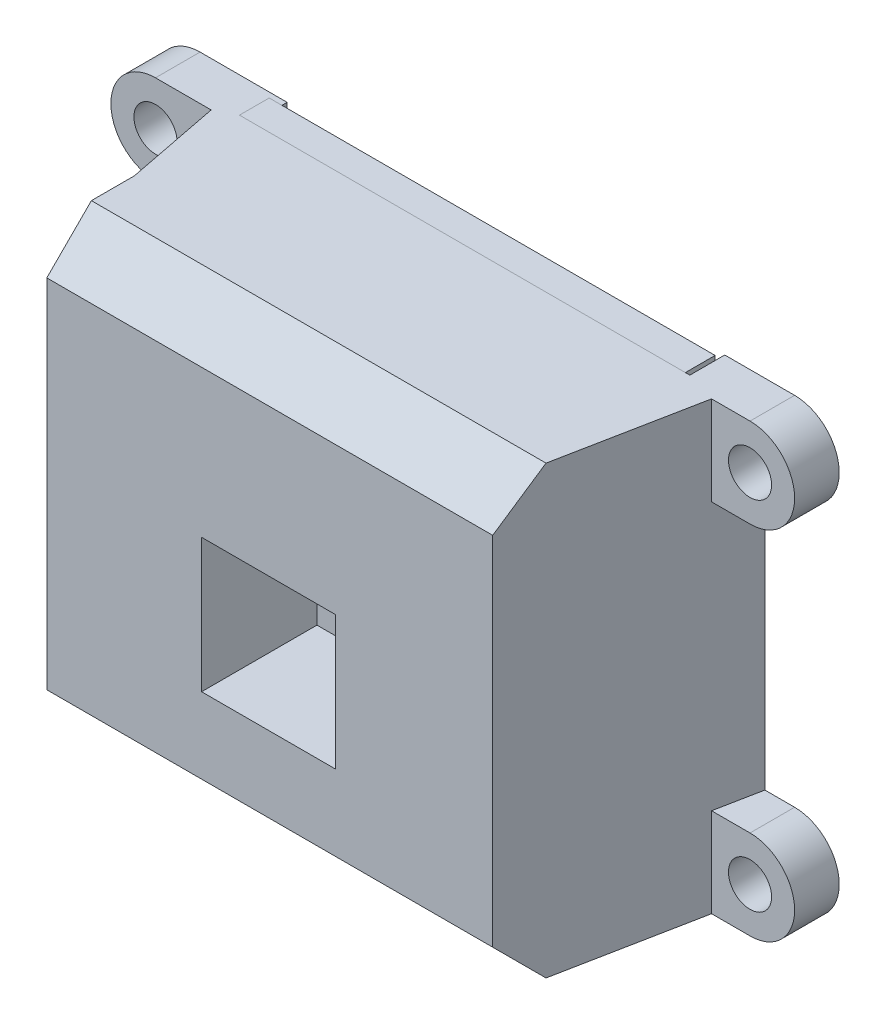
SolidWorks part; units mm, degrees
ref_plane "Front Plane" through (0, 0, 0) normal (0, 0, 1) x (1, 0, 0)
ref_plane "Top Plane" through (0, 0, 0) normal (0, 1, 0) x (1, 0, 0)
ref_plane "Right Plane" through (0, 0, 0) normal (1, 0, 0) x (0, 0, -1)
sketch "Sketch1" plane through (0, 0, 6.763) normal (0, 0, 1) x (1, 0, 0)
  line L1 (-15, -15) -> (15, -15)
  line L2 (-15, -15) -> (-15, 15)
  line L3 (-15, 15) -> (15, 15)
  line L4 (15, -15) -> (15, 15)
  line L5 (-15, -15) -> (15, 15) construction
  line L6 (-15, 15) -> (15, -15) construction
  point P0 (0, 0)
  dimension "D1" = 30
extrude "Boss-Extrude1" add sketch "Sketch1" along normal blind 2
sketch "Sketch2" plane through (0, 0, 6.763) normal (0, 0, -1) x (-1, 0, 0)
  line L0 (13, -15) -> (13, 13)
  line L1 (13, 13) -> (-13, 13)
  line L2 (-13, 13) -> (-13, -15)
  line L3 (-15, -15) -> (-13, -15)
  line L4 (-15, 15) -> (-15, -15)
  line L5 (-15, -15) -> (15, -15)
  line L6 (15, -15) -> (15, 15)
  line L7 (15, 15) -> (-15, 15)
  line L8 (-15, 15) -> (-15, -15)
  line L10 (15, -15) -> (15, 15)
  line L11 (15, 15) -> (-15, 15)
  line L12 (13, -15) -> (15, -15)
  dimension "D1" = 0
  dimension "D2" = 2
extrude "Boss-Extrude2" add sketch "Sketch2" along normal offset from surface (10.963 mm away) 1 offset beyond the face yes
sketch "Sketch3" plane through (0, 0, 6.763) normal (0, 0, -1) x (-1, 0, 0)
  line L0 (-10.4058, -0.3047) -> (-13, -0.3047)
  line L1 (-13, 13) -> (-13, -15) construction
  line L2 (-13, -0.3047) -> (-13, -4.7047)
  line L3 (-13, -4.7047) -> (-10.4058, -4.7047)
  line L4 (-13, 12.1953) -> (-10.4058, 12.1953)
  line L5 (-13, -15) -> (-13, 13) construction
  line L6 (-10.4058, 7.7953) -> (-13, 7.7953)
  line L7 (-13, 7.7953) -> (-13, 12.1953)
  line L8 (13, 12.1953) -> (10.5942, 12.1953)
  line L9 (13, 13) -> (13, -15) construction
  line L10 (10.5942, 7.7953) -> (13, 7.7953)
  line L11 (12.5942, -9.8667) -> (12.5942, 9.9953) construction
  line L12 (13, 7.7953) -> (13, 12.1953)
  line L13 (12.5942, -0.3047) -> (10.5942, -0.3047)
  line L14 (10.5942, -4.7047) -> (12.5942, -4.7047)
  line L15 (12.5942, -4.7047) -> (12.5942, -0.3047)
  arc A4 (-12.4058, -3.4212) -> (-12.4058, -1.5882) centre (-10.4058, -2.5047) ccw construction
  arc A8 (-10.4058, -4.7047) -> (-10.4058, -0.3047) centre (-10.4058, -2.5047) ccw
  arc A9 (-10.4058, 12.1953) -> (-10.4058, 7.7953) centre (-10.4058, 9.9953) cw
  arc A10 (-12.4058, 9.0788) -> (-9.4893, 11.9953) centre (-10.4058, 9.9953) ccw construction
  arc A11 (10.5942, 12.1953) -> (10.5942, 7.7953) centre (10.5942, 9.9953) ccw
  arc A12 (9.6777, 11.9953) -> (12.5942, 9.0788) centre (10.5942, 9.9953) ccw construction
  arc A13 (10.5942, -0.3047) -> (10.5942, -4.7047) centre (10.5942, -2.5047) ccw
  arc A14 (12.5942, -1.5882) -> (12.5942, -3.4212) centre (10.5942, -2.5047) ccw construction
extrude "Boss-Extrude3" add sketch "Sketch3" along normal up to surface (5.763 mm away)
sketch "Sketch4" plane through (0, 0, 6.763) normal (0, 0, -1) x (-1, 0, 0)
  line L0 (12.5942, -11.8667) -> (12.5942, 11.9953) construction
  line L1 (12.5942, -12.3667) -> (-13, -12.3667)
  line L2 (12.5942, -12.3667) -> (12.5942, -15)
  line L3 (12.5942, -15) -> (-13, -15)
  line L4 (-13, -12.3667) -> (-13, -15)
  line L5 (-10.9551, -11.8667) -> (11.2449, -11.8667) construction
  line L6 (-10.9551, -11.8667) -> (11.2449, -11.8667) construction
  dimension "D1" = 0.5
extrude "Boss-Extrude4" add sketch "Sketch4" along normal up to surface (6.763 mm away) up to plane "Front Plane"
sketch "Sketch6" plane through (0, 0, -4.2) normal (0, 0, -1) x (-1, 0, 0)
  line L1 (-15, 15) -> (15, 15)
  line L2 (-15, 15) -> (-15, -15)
  line L3 (-15, -15) -> (15, -15)
  line L4 (15, 15) -> (15, -15)
extrude "Boss-Extrude5" add sketch "Sketch6" along normal blind 2 separate body
sketch "Sketch8" plane through (0, 0, 8.763) normal (0, 0, 1) x (1, 0, 0)
  line L0 (-4.0859, 1.5922) -> (-4.0859, -6.4078) construction
  line L1 (-4.0859, -6.4078) -> (3.9141, -6.4078) construction
  line L2 (3.9141, -6.4078) -> (3.9141, 1.5922) construction
  line L3 (3.9141, 1.5922) -> (-4.0859, 1.5922) construction
  line L4 (-4.0859, 1.5922) -> (-4.0859, -6.4078) construction
  line L5 (-4.0859, -6.4078) -> (3.9141, -6.4078) construction
  line L6 (3.9141, -6.4078) -> (3.9141, 1.5922) construction
  line L7 (3.9141, 1.5922) -> (-4.0859, 1.5922) construction
  line L8 (-4.5859, 2.0922) -> (-4.5859, -6.9078)
  line L9 (-4.5859, -6.9078) -> (4.4141, -6.9078)
  line L10 (4.4141, -6.9078) -> (4.4141, 2.0922)
  line L11 (4.4141, 2.0922) -> (-4.5859, 2.0922)
  dimension "D1" = 0.5
extrude "Cut-Extrude1" cut sketch "Sketch8" against normal through all
sketch "Sketch9" plane through (0, 0, 6.763) normal (0, 0, -1) x (-1, 0, 0)
  line L0 (5.5859, -7.9078) -> (5.5859, 3.0922)
  line L1 (5.5859, 3.0922) -> (-5.4141, 3.0922)
  line L2 (-5.4141, 3.0922) -> (-5.4141, -7.9078)
  line L3 (-5.4141, -7.9078) -> (5.5859, -7.9078)
  line L4 (4.5859, -6.9078) -> (4.5859, 2.0922)
  line L5 (-4.4141, -6.9078) -> (4.5859, -6.9078)
  line L6 (-4.4141, 2.0922) -> (-4.4141, -6.9078)
  line L7 (4.5859, 2.0922) -> (-4.4141, 2.0922)
  line L8 (4.5859, -6.9078) -> (4.5859, 2.0922)
  line L9 (-4.4141, -6.9078) -> (4.5859, -6.9078)
  line L10 (-4.4141, 2.0922) -> (-4.4141, -6.9078)
  line L11 (4.5859, 2.0922) -> (-4.4141, 2.0922)
  dimension "D1" = 0
  dimension "D2" = 1
extrude "Boss-Extrude7" add sketch "Sketch9" along normal up to surface (5.763 mm away)
sketch "Sketch10" plane through (0, 0, 1) normal (0, 0, -1) x (-1, 0, 0)
  line L0 (5.5859, 3.0922) -> (-5.4141, 3.0922) construction
  line L1 (4.5859, 2.0922) -> (-4.4141, 2.0922)
  line L2 (4.5859, 2.0922) -> (4.5859, 3.0922)
  line L3 (4.5859, 3.0922) -> (-4.4141, 3.0922)
  line L4 (-4.4141, 2.0922) -> (-4.4141, 3.0922)
extrude "Cut-Extrude2" cut sketch "Sketch10" against normal offset from surface (2.1 mm away) 1 offset beyond the face yes
sketch "Sketch11" plane through (0, 0, 6.763) normal (0, 0, -1) x (-1, 0, 0)
  line L1 (-13, 13) -> (12.5942, 13)
  line L2 (-13, 13) -> (-13, 11.9953)
  line L3 (-13, 11.9953) -> (12.5942, 11.9953)
  line L4 (12.5942, 13) -> (12.5942, 11.9953)
  line L5 (12.5942, -11.8667) -> (12.5942, 11.9953) construction
  line L6 (-10.4058, 11.9953) -> (10.5942, 11.9953) construction
extrude "Boss-Extrude8" add sketch "Sketch11" along normal up to surface (10.963 mm away) up to face at (0, -0.5, -4.2)
sketch "Sketch13" plane through (0, -15, 0) normal (0, -1, 0) x (1, 0, 0)
  line L0 (13, -4.2) -> (15, -4.2) construction
  line L1 (13.75, -4.2) -> (13, -4.2)
  line L2 (13.75, -4.2) -> (13.75, 0)
  line L3 (13.75, 0) -> (13, 0)
  line L4 (13, -4.2) -> (13, 0)
  line L5 (13, -4.2) -> (13, 0) construction
  line L6 (-12.5942, 0) -> (13, 0) construction
  line L7 (15, 8.763) -> (15, -4.2) construction
  line L9 (-13.3442, -4.2) -> (-12.5942, -4.2)
  line L10 (-13.3442, -4.2) -> (-13.3442, 0)
  line L11 (-13.3442, 0) -> (-12.5942, 0)
  line L12 (-12.5942, -4.2) -> (-12.5942, 0)
  line L13 (-15, -4.2) -> (-13, -4.2) construction
  point P8 (-12.5942, 0)
  dimension "D1" = 1.25
extrude "Cut-Extrude3" cut sketch "Sketch13" against normal up to surface (26.9953 mm away) up to face at (0.0543, 11.9953, 1.1407)
sketch "Sketch7" plane through (0, -15, 0) normal (0, -1, 0) x (1, 0, 0)
  line L0 (15, -4.2) -> (-15, -4.2) construction
  line L1 (13.5, -4.2) -> (-13.0942, -4.2)
  line L2 (13.5, -4.2) -> (13.5, -0.25)
  line L3 (13.5, -0.25) -> (-13.0942, -0.25)
  line L4 (-13.0942, -4.2) -> (-13.0942, -0.25)
  line L5 (13.75, -0.25) -> (13.5, -0.25) construction
  line L7 (13.5, 0) -> (13.5, -0.25) construction
  line L8 (-12.5942, 0) -> (13.75, 0) construction
  line L9 (-13.3442, -0.25) -> (-13.0942, -0.25) construction
  line L11 (13.75, -4.2) -> (13.75, 0) construction
  line L12 (-13.3442, 0) -> (-13.3442, -4.2) construction
  dimension "D1" = 0.25
extrude "Boss-Extrude6" add sketch "Sketch7" against normal blind 2
sketch "Sketch12" plane through (0, -15, 0) normal (0, -1, 0) x (1, 0, 0)
  line L0 (13.5, -0.25) -> (-13.0942, -0.25) construction
  line L1 (-12.0942, -0.25) -> (-13.0942, -0.25)
  line L2 (-12.0942, -0.25) -> (-12.0942, -4.2)
  line L3 (-12.0942, -4.2) -> (-13.0942, -4.2)
  line L4 (-13.0942, -0.25) -> (-13.0942, -4.2)
  line L6 (12.5, -0.25) -> (13.5, -0.25)
  line L7 (12.5, -0.25) -> (12.5, -4.2)
  line L8 (12.5, -4.2) -> (13.5, -4.2)
  line L9 (13.5, -0.25) -> (13.5, -4.2)
  dimension "D1" = 1
extrude "Boss-Extrude10" add sketch "Sketch12" against normal up to surface (26.9953 mm away) up to face at (2.7935, 11.9953, 0.9126)
sketch "Sketch14" plane through (0, 0, -0.25) normal (0, 0, 1) x (1, 0, 0)
  line L0 (-13.1199, -12.8419) -> (-13.5415, -11.577)
  line L1 (-13.0942, 11.9953) -> (-13.0942, -15) construction
  line L2 (-13.5415, -11.2607) -> (-13.1199, -9.9958)
  line L3 (-13.0942, -15) -> (-13.0942, -13) construction
  line L4 (-13.0942, 11.9953) -> (-13.0942, -15) construction
  line L5 (-13.0942, -9.8377) -> (-13.0942, -9.3077) construction
  line L6 (-13.5942, -11.4189) -> (-13.0942, -11.4189) construction
  line L7 (-13.0942, -9.9189) -> (-13.0942, -12.9189) construction
  line L8 (-13.0942, -9.8377) -> (-13.0942, -13)
  line L9 (12.5, -13) -> (-12.0942, -13) construction
  line L10 (0, 0) -> (0, -9.9686) construction
  line L11 (13.0942, -9.9189) -> (13.0942, -12.9189) construction
  line L12 (13.5942, -11.4189) -> (13.0942, -11.4189) construction
  line L13 (13.0942, -9.8377) -> (13.0942, -9.3077) construction
  line L14 (13.0942, -15) -> (13.0942, -13) construction
  line L15 (13.0942, -9.8377) -> (13.0942, -13)
  line L16 (13.5415, -11.2607) -> (13.1199, -9.9958)
  line L17 (13.1199, -12.8419) -> (13.5415, -11.577)
  arc A0 (-13.1199, -12.8419) -> (-13.0942, -13) centre (-13.5942, -13) cw
  arc A1 (-13.5415, -11.577) -> (-13.5415, -11.2607) centre (-13.0672, -11.4189) cw
  arc A2 (-13.1199, -9.9958) -> (-13.0942, -9.8377) centre (-13.5942, -9.8377) ccw
  arc A3 (13.1199, -9.9958) -> (13.0942, -9.8377) centre (13.5942, -9.8377) cw
  arc A4 (13.5415, -11.577) -> (13.5415, -11.2607) centre (13.0672, -11.4189) ccw
  arc A5 (13.1199, -12.8419) -> (13.0942, -13) centre (13.5942, -13) ccw
  dimension "D3" = 0.5
  dimension "D1" = 0.5
  dimension "D2" = 3
extrude "Boss-Extrude11" add sketch "Sketch14" against normal up to surface (3.95 mm away) up to face at (0.1353, -0.6682, -4.2)
sketch "Sketch16" plane through (0, 0, -4.2) normal (0, 0, 1) x (1, 0, 0)
  line L0 (-13.2147, -9.9642) -> (-13.6364, -11.2291)
  line L1 (-13.6364, -11.6086) -> (-13.2147, -12.8735)
  line L2 (-13.2147, -9.9642) -> (-13.0942, -9.6026)
  line L3 (-13.5415, -11.577) -> (-13.1199, -12.8419)
  line L4 (-13.0942, -13) -> (-13.0942, -9.8377)
  line L5 (-13.1199, -9.9958) -> (-13.5415, -11.2607)
  line L6 (-13.5415, -11.577) -> (-13.1199, -12.8419) construction
  line L7 (-13.0942, -13) -> (-13.0942, -9.8377) construction
  line L8 (-13.1199, -9.9958) -> (-13.5415, -11.2607) construction
  line L9 (-13.0942, -9.6026) -> (-13.0942, -13.2351)
  line L10 (-13.0942, -13.2351) -> (-13.2147, -12.8735)
  line L11 (0, 0) -> (0, -6.6322) construction
  line L12 (13.0942, -9.6026) -> (13.0942, -13.2351)
  line L13 (13.2147, -9.9642) -> (13.0942, -9.6026)
  line L14 (13.2147, -9.9642) -> (13.6364, -11.2291)
  line L15 (13.6364, -11.6086) -> (13.2147, -12.8735)
  line L16 (13.0942, -13.2351) -> (13.2147, -12.8735)
  arc A0 (-13.6364, -11.2291) -> (-13.6364, -11.6086) centre (-13.0672, -11.4189) ccw
  arc A1 (13.6364, -11.2291) -> (13.6364, -11.6086) centre (13.0672, -11.4189) cw
  arc A3 (-13.0942, -13) -> (-13.1199, -12.8419) centre (-13.5942, -13) ccw
  arc A4 (-13.1199, -9.9958) -> (-13.0942, -9.8377) centre (-13.5942, -9.8377) ccw
  arc A5 (-13.5415, -11.2607) -> (-13.5415, -11.577) centre (-13.0672, -11.4189) ccw
  arc A6 (-13.0942, -13) -> (-13.1199, -12.8419) centre (-13.5942, -13) ccw construction
  arc A7 (-13.1199, -9.9958) -> (-13.0942, -9.8377) centre (-13.5942, -9.8377) ccw construction
  arc A8 (-13.5415, -11.2607) -> (-13.5415, -11.577) centre (-13.0672, -11.4189) ccw construction
  arc A9 (-13.1942, -13) -> (-13.2147, -12.8735) centre (-13.5942, -13) ccw construction
  dimension "D1" = 0
  dimension "D2" = 0.1
extrude "Cut-Extrude4" cut sketch "Sketch16" along normal up to surface (4.2 mm away) up to face at (4.7186, -5.1238, 0)
sketch "Sketch17" plane through (0, -15, 0) normal (0, -1, 0) x (1, 0, 0)
  line L0 (15, 8.763) -> (18, -6.55)
  line L1 (18, -6.55) -> (15.3, -6.55)
  line L2 (15.3, -6.55) -> (15.3, -4.2)
  line L3 (15.3, -4.2) -> (15, -4.2)
  line L4 (15, -4.2) -> (15, 8.763)
  line L5 (15, -6.2) -> (15, -4.2) construction
  line L7 (15, 8.763) -> (15, -4.2) construction
  line L8 (0.5779, 0) -> (0.5779, 4.7808) construction
  line L9 (-12.5942, 0) -> (13.75, 0) construction
  line L10 (-14.1442, -4.2) -> (-13.8442, -4.2)
  line L11 (-14.1442, -6.55) -> (-14.1442, -4.2)
  line L12 (-16.8442, -6.55) -> (-14.1442, -6.55)
  line L13 (-13.8442, 8.763) -> (-16.8442, -6.55)
  line L14 (-13.8442, -4.2) -> (-13.8442, 8.763)
  line L15 (15, -6.2) -> (-15, -6.2) construction
  dimension "D1" = 0.3
  dimension "D2" = 3
  dimension "D3" = 0.35
extrude "Boss-Extrude12" add sketch "Sketch17" against normal up to surface (30 mm away) up to face at (0, 15, 2.2815)
sketch "Sketch18" plane through (0, 0, -6.55) normal (0, 0, -1) x (-1, 0, 0)
  line L1 (-20, -12) -> (20, -12)
  line L2 (-20, -12) -> (-20, 12)
  line L3 (-20, 12) -> (20, 12)
  line L4 (20, -12) -> (20, 12)
  line L5 (-20, -12) -> (20, 12) construction
  line L6 (-20, 12) -> (20, -12) construction
  point P0 (0, 0)
  dimension "D1" = 40
  dimension "D2" = 24
sketch "Sketch19" plane through (0, 0, -6.55) normal (0, 0, -1) x (-1, 0, 0)
  line L0 (-15.3, 15) -> (-20, 15)
  line L1 (-20, -12) -> (-20, 12) construction
  line L2 (-20, 9) -> (-15.3, 9)
  line L4 (-15.3, 9) -> (-15.3, 15)
  line L5 (14.1442, 15) -> (20, 15)
  line L6 (20, 9) -> (14.1442, 9)
  line L8 (14.1442, 9) -> (14.1442, 15)
  line L9 (-15.3, -15) -> (-20, -15)
  line L10 (-20, -9) -> (-15.3, -9)
  line L11 (-15.3, -9) -> (-15.3, -15)
  line L12 (14.1442, -15) -> (20, -15)
  line L13 (20, -12) -> (20, 12) construction
  line L14 (20, -9) -> (14.1442, -9)
  line L15 (14.1442, -9) -> (14.1442, -15)
  line L16 (-15.3, 15) -> (-15.3, -15) construction
  arc A0 (-20, 15) -> (-20, 9) centre (-20, 12) ccw
  arc A1 (20, 15) -> (20, 9) centre (20, 12) cw
  arc A2 (-20, -15) -> (-20, -9) centre (-20, -12) cw
  arc A3 (20, -15) -> (20, -9) centre (20, -12) ccw
extrude "Boss-Extrude13" add sketch "Sketch19" against normal blind 3
hole_wizard "M2.5 Clearance Hole1" positions "Sketch20" profile "Sketch21" hole size "M2.5" standard "ANSI Metric" end condition through all
sketch "Sketch20" plane through (0, 0, -3.55) normal (0, 0, 1) x (1, 0, 0)
  point P0 (-20, 12)
  point P3 (20, 12)
  point P6 (20, -12)
  point P9 (-20, -12)
sketch "Sketch21" plane through (-20, 12, -3.55) normal (1, 0, 0) x (0, -1, 0)
  line L0 (0, 0) -> (0, 3)
  line L1 (0, 3) -> (1.45, 3)
  line L2 (1.45, 3) -> (1.45, 0)
  line L5 (1.45, 0) -> (0, 0)
  line L11 (0, -6.35) -> (0, 107.95) construction
  dimension "Thru Hole Dia." = 2.9
  dimension "Thru Hole Depth" = 3
chamfer "Chamfer1" distance 3 angle 45 2 edges at (0, 15, 8.763) (0, -15, 8.763)
sketch "Sketch22" plane through (0, -15, 0) normal (0, -1, 0) x (1, 0, 0)
  line L0 (13.5, -0.25) -> (-13.0942, -0.25) construction
  line L1 (-9.2449, -0.25) -> (9.6507, -0.25)
  line L2 (-9.2449, -0.25) -> (-9.2449, -1.9)
  line L3 (-9.2449, -1.9) -> (9.6507, -1.9)
  line L4 (9.6507, -0.25) -> (9.6507, -1.9)
  line L5 (8.1551, -1.4) -> (-8.2449, -1.4) construction
  line L6 (8.1551, -1.4) -> (-8.2449, -1.4) construction
  line L7 (-8.2449, 0) -> (-8.2449, -1.4) construction
  line L8 (-8.2449, 0) -> (-8.2449, -1.4) construction
  point P4 (0.2029, -0.25)
  dimension "D1" = 0.5
  dimension "D2" = 1
extrude "Cut-Extrude5" cut sketch "Sketch22" against normal up to surface (2 mm away) up to face at (0.2029, -13, -2.225)
